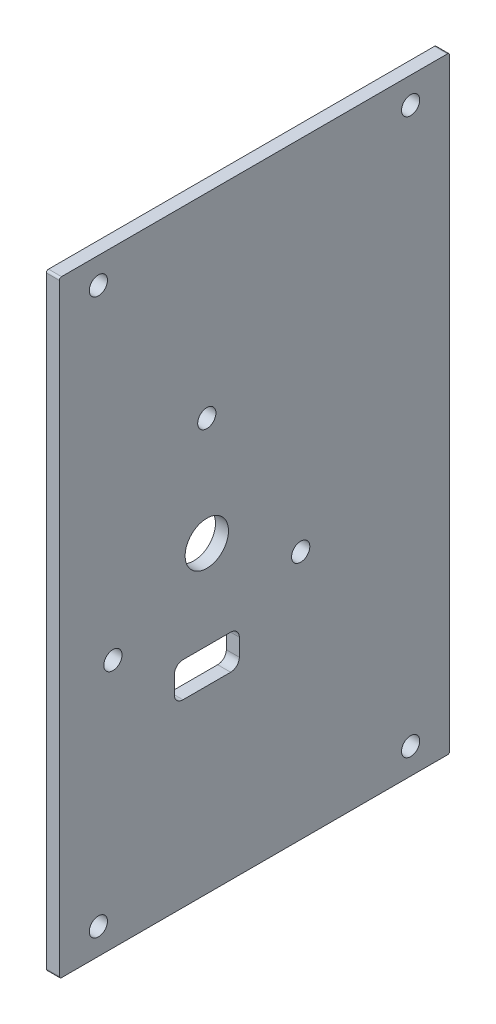
SolidWorks part; units mm, degrees
material "ABS"
ref_plane "Front Plane" through (0, 0, 0) normal (0, 0, 1) x (1, 0, 0)
ref_plane "Top Plane" through (0, 0, 0) normal (0, 1, 0) x (1, 0, 0)
ref_plane "Right Plane" through (0, 0, 0) normal (1, 0, 0) x (0, 0, -1)
sketch "Sketch1" plane through (0, 0, 0) normal (1, 0, 0) x (0, 0, -1)
  line L0 (34, -90.5) -> (28.5, -90.5)
  line L1 (0, 0) -> (90, 0)
  line L2 (0, 0) -> (0, -140)
  line L3 (0, -140) -> (90, -140)
  line L4 (90, 0) -> (90, -140)
  line L5 (26.5, -92.5) -> (26.5, -96.5)
  line L6 (34, -70) -> (34, -90.5) construction
  line L7 (28.5, -98.5) -> (39.5, -98.5)
  line L8 (41.5, -96.5) -> (41.5, -92.5)
  line L9 (39.5, -90.5) -> (34, -90.5)
  line L10 (45, 0) -> (45, -140) construction
  line L11 (0, -70) -> (90, -70) construction
  circle A0 centre (34, -70) radius 5
  circle A1 centre (34, -45) radius 2.1
  circle A2 centre (55.6506, -82.5) radius 2.1
  circle A3 centre (12.3494, -82.5) radius 2.1
  arc A4 (41.5, -96.5) -> (39.5, -98.5) centre (39.5, -96.5) cw
  arc A5 (39.5, -90.5) -> (41.5, -92.5) centre (39.5, -92.5) cw
  arc A6 (28.5, -98.5) -> (26.5, -96.5) centre (28.5, -96.5) cw
  arc A7 (26.5, -92.5) -> (28.5, -90.5) centre (28.5, -92.5) cw
  circle A8 centre (9, -6) radius 2.1
  circle A9 centre (81, -6) radius 2.1
  circle A10 centre (81, -134) radius 2.1
  circle A11 centre (9, -134) radius 2.1
  point P21 (41.5, -98.5)
  point P26 (26.5, -98.5)
  point P29 (26.5, -90.5)
  dimension "D5" = 10
  dimension "D7" = 4.2
  dimension "D13" = 2
  dimension "D17" = 4.2
  dimension "D3" = 70
  dimension "D4" = 34
  dimension "D6" = 25
  dimension "D9" = 20.5
  dimension "D10" = 7.5
  dimension "D11" = 15
  dimension "D12" = 8
  dimension "D14" = 90
  dimension "D2" = 140
  dimension "D15" = 9
  dimension "D16" = 6
  dimension "D8" = 3
extrude "Boss-Extrude1" add sketch "Sketch1" along normal blind 3
fillet "Fillet1" radius 0.5 4 edges at (1.5, -140, -90) (1.5, -140, 0) (1.5, 0, -90) (1.5, 0, 0)
equation "\"Depth\"= 90mm"
equation "\"Height\"= 140mm"
equation "\"Width\"= 64mm"
equation "\"D14@Sketch1\"=\"Depth\""
equation "\"D2@Sketch1\"=\"Height\""
